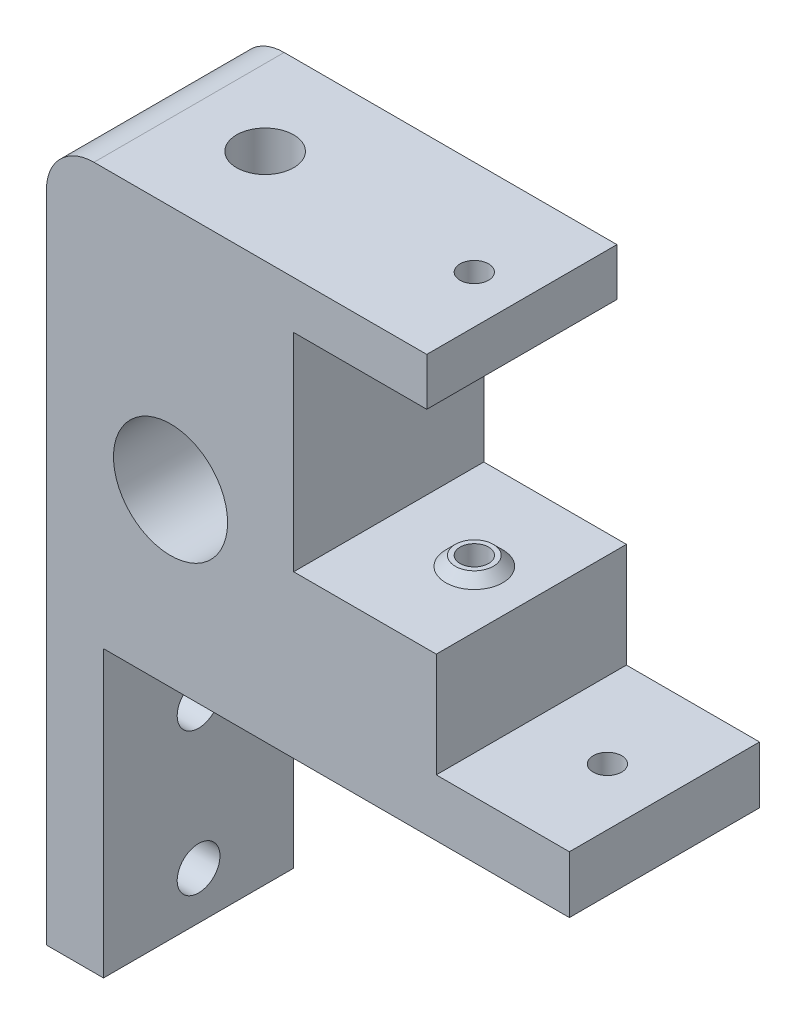
SolidWorks part; units mm, degrees
ref_plane "Front Plane" through (0, 0, 0) normal (0, 0, 1) x (1, 0, 0)
ref_plane "Top Plane" through (0, 0, 0) normal (0, 1, 0) x (1, 0, 0)
ref_plane "Right Plane" through (0, 0, 0) normal (1, 0, 0) x (0, 0, -1)
sketch "Sketch1" plane through (0, 0, 0) normal (0, 0, 1) x (1, 0, 0)
  line L0 (27, 30.8) -> (27, 25.8)
  line L1 (-13, 30.8) -> (27, 30.8)
  line L2 (-13, 30.8) -> (-13, -8.2915)
  line L5 (27, 25.8) -> (13, 25.8)
  line L6 (-7, -13) -> (42, -13)
  line L8 (-13, -8.2915) -> (-13, -43)
  line L9 (-13, -43) -> (-7, -43)
  line L10 (-7, -13) -> (-7, -43)
  line L13 (13, -7) -> (42, -7)
  line L14 (42, -13) -> (42, -7)
  line L15 (13, 25.8) -> (13, -7)
  line L16 (31, 24.8) -> (13, 24.8) construction
  circle A0 centre (0.0517, 5) radius 6
  dimension "D1" = 12
  dimension "D10" = 13
  dimension "D11" = 18
  dimension "D2" = 5
  dimension "D3" = 40
  dimension "D4" = 30
  dimension "D5" = 6
  dimension "D6" = 6
  dimension "D7" = 1
  dimension "D8" = 13
  dimension "D9" = 13
  dimension "D12" = 5.0003
  dimension "D13" = 15
extrude "Boss-Extrude1" add sketch "Sketch1" along normal blind 20
sketch "Sketch2" plane through (-13, 0, 0) normal (-1, 0, 0) x (0, 0, 1)
  line L0 (20, -43) -> (0, -43) construction
  circle A0 centre (10, -38) radius 2.25
  circle A1 centre (10, -23) radius 2.25
  dimension "D2" = 4.5
  dimension "D3" = 4.5
  dimension "D1" = 5
  dimension "D4" = 15
extrude "Cut-Extrude1" cut sketch "Sketch2" against normal blind 20
sketch "Sketch4" plane through (0, 30.8, 0) normal (0, 1, 0) x (1, 0, 0)
  line L0 (27, 0) -> (-13, 0) construction
  line L1 (42, 0) -> (13, 0) construction
  line L2 (42, -20) -> (42, 0) construction
  line L3 (-13, -20) -> (-13, 0) construction
  circle A0 centre (22, -10) radius 1.5
  circle A1 centre (36, -10) radius 1.5
  dimension "D3" = 3
  dimension "D1" = 10
  dimension "D2" = 10
  dimension "D4" = 6
  dimension "D5" = 35
extrude "Cut-Extrude2" cut sketch "Sketch4" against normal blind 45
sketch "Sketch5" plane through (0, -7, 0) normal (0, 1, 0) x (1, 0, 0)
  line L0 (42, -20) -> (13, -20) construction
  line L1 (28, 0) -> (12.7113, 0)
  line L2 (28, 0) -> (28, -20)
  line L3 (28, -20) -> (12.7113, -20)
  line L4 (12.7113, 0) -> (12.7113, -20)
  circle A1 centre (22, -10) radius 1.5
  point P0 (22, -10)
  dimension "D1" = 6
  dimension "D2" = 3
extrude "Boss-Extrude2" add sketch "Sketch5" along normal offset from surface (11 mm away) 1
sketch "Sketch6" plane through (0, 30.8, 0) normal (0, 1, 0) x (1, 0, 0)
  line L0 (-13, -20) -> (-13, 0) construction
  line L1 (27, 0) -> (-13, 0) construction
  circle A0 centre (0, -10) radius 1.25
  dimension "D2" = 10
  dimension "D3" = 2.5
  dimension "D1" = 13
extrude "Cut-Extrude3" cut sketch "Sketch6" against normal up to next
sketch "Sketch7" plane through (0, 30.8, 0) normal (0, 1, 0) x (1, 0, 0)
  circle A0 centre (0, -10) radius 3
  dimension "D1" = 6
extrude "Cut-Extrude4" cut sketch "Sketch7" against normal blind 5
sketch "Sketch9" plane through (0, -13, 0) normal (0, -1, 0) x (1, 0, 0)
  line L1 (25.2332, 10) -> (23.6166, 12.8)
  line L2 (23.6166, 12.8) -> (20.3834, 12.8)
  line L3 (20.3834, 12.8) -> (18.7668, 10)
  line L4 (18.7668, 10) -> (20.3834, 7.2)
  line L5 (20.3834, 7.2) -> (23.6166, 7.2)
  line L6 (23.6166, 7.2) -> (25.2332, 10)
  circle A0 centre (22, 10) radius 2.8 construction
  dimension "D1" = 5.6
extrude "Cut-Extrude5" cut sketch "Sketch9" against normal blind 5
fillet "Fillet1" radius 5 1 edges at (-13, 30.8, 10)
fillet "Fillet2" [suppressed] radius 2
sketch "Sketch10" plane through (0, 4, 0) normal (0, 1, 0) x (1, 0, 0)
  circle A0 centre (22, -10) radius 1.5
  circle A1 centre (22, -10) radius 3
  point P4 (0, 0)
  dimension "D1" = 6
  dimension "D2" = 3
extrude "Boss-Extrude3" add sketch "Sketch10" along normal blind 1
chamfer "Chamfer1" distance 1 angle 45 1 edges at (19, 5, 10)
sketch "Sketch11" plane through (0, 25.8, 0) normal (0, -1, 0) x (1, 0, 0)
  circle A0 centre (22, 10) radius 1.5
  circle A1 centre (22, 10) radius 3
  dimension "D1" = 6
extrude "Boss-Extrude4" add sketch "Sketch11" along normal blind 1
chamfer "Chamfer2" distance 1 angle 45 1 edges at (25, 24.8, 10)
